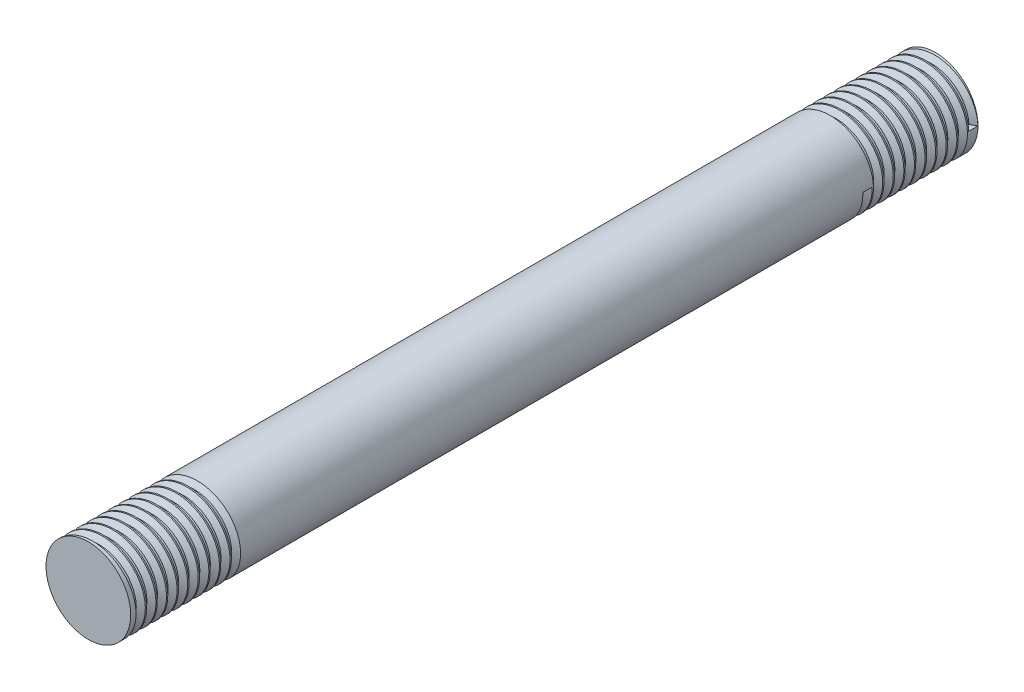
SolidWorks part; units mm, degrees
ref_plane "Front Plane" through (0, 0, 0) normal (0, 0, 1) x (1, 0, 0)
ref_plane "Top Plane" through (0, 0, 0) normal (0, 1, 0) x (1, 0, 0)
ref_plane "Right Plane" through (0, 0, 0) normal (1, 0, 0) x (0, 0, -1)
sketch "Sketch1" plane through (0, 0, 0) normal (0, 0, 1) x (1, 0, 0)
  circle A0 centre (0, 0) radius 4
extrude "Boss-Extrude1" add sketch "Sketch1" along normal blind 80
thread "Thread1" pitch 1 method cut profile "Thread Profile1" start angle 0, offset 0, length 10, pitch 1, diameter 8
ref_plane "Plane1" through (-4, 0, 80) normal (0, -1, 0) x (-1, 0, 0)
sketch "Thread Profile1" plane through (-4, 0, 80) normal (0, -1, 0) x (-1, 0, 0)
  line L0 (0, 0) -> (0, 1) construction
  line L11 (0, 0) -> (0, 0.875)
  line L12 (0, 0.875) -> (-0.5413, 0.5625)
  line L13 (-0.5413, 0.5625) -> (-0.5413, 0.3125)
  line L15 (-0.5413, 0.3125) -> (0, 0)
  line L17 (-0.5413, 0.4375) -> (0, 0.4375) construction
  point P2 (0, 0)
  dimension "Pitch" = 1
  dimension "Profile_Angle" = 60
  dimension "Profile_Land" = 0.25
  dimension "Profile_Height" = 0.5413
thread "Thread2" pitch 1 method cut profile "Thread Profile2" start angle 0, offset 0, length 10, pitch 1, diameter 8
ref_plane "Plane2" through (4, 0, 0) normal (0, -1, 0) x (1, 0, 0)
sketch "Thread Profile2" plane through (4, 0, 0) normal (0, -1, 0) x (1, 0, 0)
  line L0 (0, 0) -> (0, 1) construction
  line L11 (0, 0) -> (0, 0.875)
  line L12 (0, 0.875) -> (-0.5413, 0.5625)
  line L13 (-0.5413, 0.5625) -> (-0.5413, 0.3125)
  line L15 (-0.5413, 0.3125) -> (0, 0)
  line L17 (-0.5413, 0.4375) -> (0, 0.4375) construction
  point P2 (0, 0)
  dimension "Pitch" = 1
  dimension "Profile_Angle" = 60
  dimension "Profile_Land" = 0.25
  dimension "Profile_Height" = 0.5413
